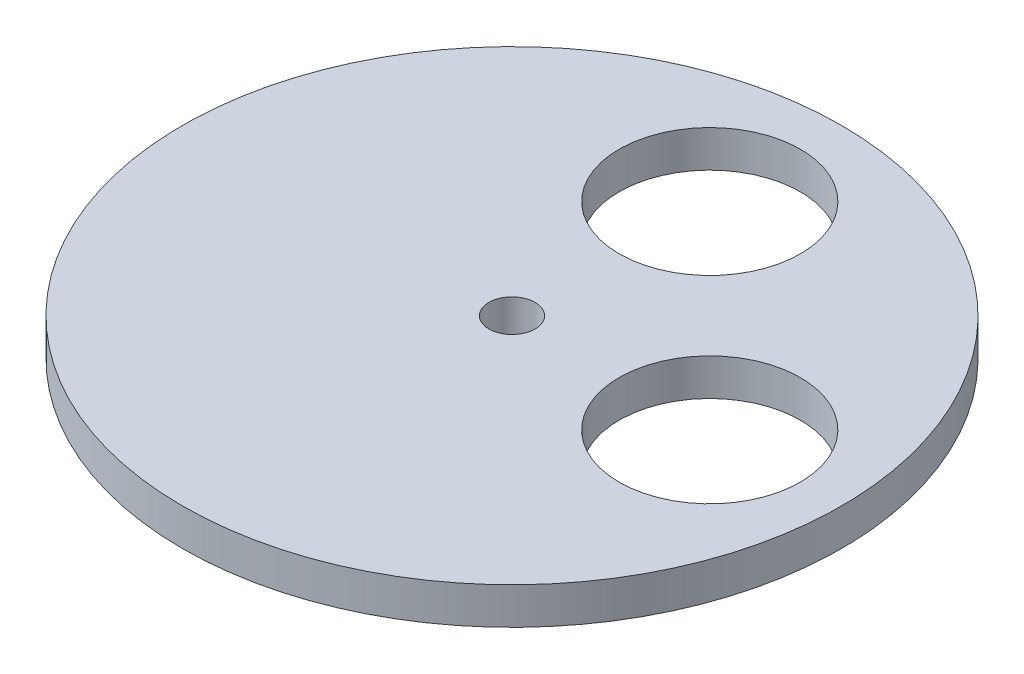
SolidWorks part; units mm, degrees
ref_plane "Front Plane" through (0, 0, 0) normal (0, 0, 1) x (1, 0, 0)
ref_plane "Top Plane" through (0, 0, 0) normal (0, 1, 0) x (1, 0, 0)
ref_plane "Right Plane" through (0, 0, 0) normal (1, 0, 0) x (0, 0, -1)
sketch "Sketch6" plane through (0, 0, 0) normal (0, 1, 0) x (1, 0, 0)
  circle A2 centre (63.5, 63.5) radius 63.5
  point P2 (0, 0)
  point P4 (-1.6189, -1.1366)
  dimension "D1" = 127
extrude "Boss-Extrude3" add sketch "Sketch6" along normal blind 7.112 contours A2
sketch "Sketch8" plane through (0, 7.112, 0) normal (0, 1, 0) x (1, 0, 0)
sketch "Sketch11" plane through (0, 7.112, 0) normal (0, 1, 0) x (1, 0, 0)
  line L0 (63.5, 127) -> (63.5, 63.5)
  line L1 (63.5, 63.5) -> (127, 63.5)
  circle A0 centre (63.5, 101.6066) radius 17.4625
  circle A1 centre (101.6, 63.5) radius 17.4625
  circle A2 centre (63.5, 63.5) radius 63.5 construction
  point P11 (0, 0)
  point P12 (0, 0)
  point P13 (0, 0)
  point P14 (0, 0)
  point P15 (0, 0)
  point P16 (0, 0)
  point P17 (63.5, 127)
  dimension "D1" = 34.925
  dimension "D4" = 34.925
  dimension "D2" = 25.3934
  dimension "D3" = 25.4
extrude "Cut-Extrude2" cut sketch "Sketch11" against normal through all contours L0 A0 | L0 A0 | L1 A1 | L1 A1 | A0 region at (70.9113, 7.112, -101.6066) region at (101.6, 7.112, -70.9113) region at (101.6, 7.112, -56.0887) region at (56.0887, 7.112, -101.6066)
sketch "Sketch12" plane through (0, 7.112, 0) normal (0, 1, 0) x (1, 0, 0)
  circle A0 centre (63.5, 63.5) radius 4.445
  dimension "D1" = 8.89
extrude "Cut-Extrude3" cut sketch "Sketch12" against normal through all contours A0
